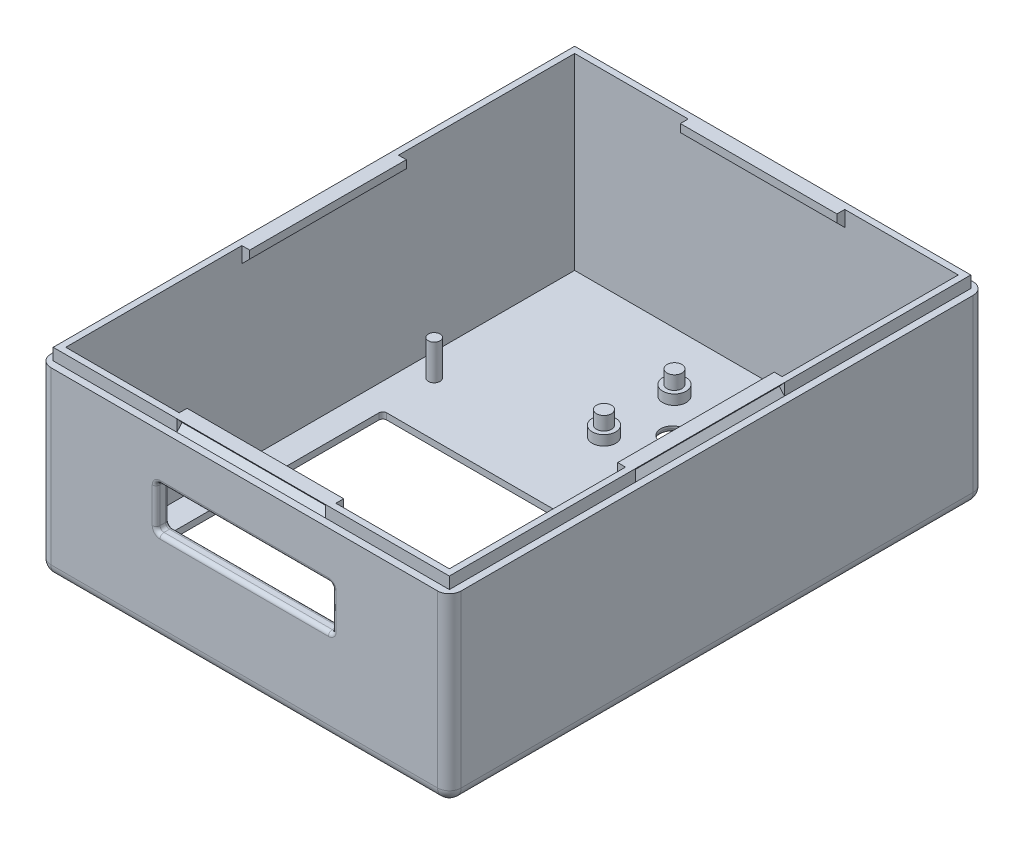
SolidWorks part; units mm, degrees
ref_plane "Plan de face" through (0, 0, 0) normal (0, 0, 1) x (1, 0, 0)
ref_plane "Plan de dessus" through (0, 0, 0) normal (0, 1, 0) x (1, 0, 0)
ref_plane "Plan de droite" through (0, 0, 0) normal (1, 0, 0) x (0, 0, -1)
sketch "Esquisse6" plane through (0, 0, 0) normal (0, 1, 0) x (1, 0, 0)
  line L1 (-49, -65) -> (49, -65)
  line L2 (-49, -65) -> (-49, 65)
  line L3 (-49, 65) -> (49, 65)
  line L4 (49, -65) -> (49, 65)
  line L5 (-49, -65) -> (49, 65) construction
  line L6 (-49, 65) -> (49, -65) construction
  point P1 (0, 0)
  dimension "D1" = 98
  dimension "D2" = 130
extrude "Boss.-Extru.4" add sketch "Esquisse6" along normal blind 48 contours L2 L3 L4 L1
shell "Coque7" thickness 1.6 removed face at (0, 48, 0) outward yes
sketch "Esquisse7" plane through (0, 0, 0) normal (0, 1, 0) x (1, 0, 0)
  line L1 (-49, -65) -> (49, -65)
  line L2 (-49, -65) -> (-49, 65)
  line L3 (-49, 65) -> (49, 65)
  line L4 (49, -65) -> (49, 65)
  line L5 (-49, -65) -> (49, 65) construction
  line L6 (-49, 65) -> (49, -65) construction
  point P0 (0, 0)
  dimension "D1" = 98
  dimension "D2" = 130
extrude "Extru.-Mince1" add sketch "Esquisse7" along normal blind 45 and the other way blind 1.6 separate body thin thin type one direction wall 3.4
sketch "Esquisse13" plane through (0, -1.6, 0) normal (0, -1, 0) x (-1, 0, 0)
  line L0 (0, -22.25) -> (-49, -22.25) construction
  line L1 (-49, 65) -> (49, 65)
  line L2 (-49, 65) -> (-49, -65)
  line L3 (-49, -65) -> (49, -65)
  line L4 (49, 65) -> (49, -65)
  line L5 (-49, 65) -> (49, -65) construction
  line L6 (-49, -65) -> (49, 65) construction
  line L7 (42.5, -54) -> (-42.5, -54)
  line L8 (42.5, -54) -> (42.5, 9.5)
  line L9 (42.5, 9.5) -> (-42.5, 9.5)
  line L10 (-42.5, -54) -> (-42.5, 9.5)
  line L11 (42.5, -54) -> (-42.5, 9.5) construction
  line L12 (42.5, 9.5) -> (-42.5, -54) construction
  line L13 (0, -22.25) -> (49, -22.25) construction
  line L15 (46.1493, 17.8641) -> (-46.1493, 17.8641) construction
  line L16 (46.1493, 17.8641) -> (46.1493, -62.3641) construction
  line L17 (46.1493, -62.3641) -> (-46.1493, -62.3641) construction
  line L18 (-46.1493, 17.8641) -> (-46.1493, -62.3641) construction
  line L19 (46.1493, 17.8641) -> (-46.1493, -62.3641) construction
  line L20 (46.1493, -62.3641) -> (-46.1493, 17.8641) construction
  point P4 (0, 0)
  point P11 (0, -22.25)
  dimension "D1" = 85
  dimension "D2" = 63.5
  dimension "D3" = 11
extrude "Enlèv. mat.-Extru.10" cut sketch "Esquisse13" against normal blind 8 contours L8 L9 L10 L7
sketch "Esquisse16" plane through (0, 0, 0) normal (0, 1, 0) x (1, 0, 0)
  line L0 (0, -18.875) -> (49, -18.875) construction
  line L1 (49, -65) -> (-49, -65) construction
  line L2 (49, -65) -> (49, 65) construction
  line L3 (49, 65) -> (-49, 65) construction
  line L4 (-49, -65) -> (-49, 65) construction
  line L5 (49, -65) -> (-49, 65) construction
  line L6 (49, 65) -> (-49, -65) construction
  line L7 (43.125, -61) -> (-43.125, -61) construction
  line L8 (43.125, -61) -> (43.125, 23.25) construction
  line L9 (43.125, 23.25) -> (-43.125, 23.25) construction
  line L10 (-43.125, -61) -> (-43.125, 23.25) construction
  line L11 (43.125, -61) -> (-43.125, 23.25) construction
  line L12 (43.125, 23.25) -> (-43.125, -61) construction
  line L13 (0, -18.875) -> (-49, -18.875) construction
  circle A0 centre (43.125, 23.25) radius 1.5
  circle A1 centre (43.125, -61) radius 1.5
  circle A2 centre (-43.125, -61) radius 1.5
  circle A3 centre (-43.125, 23.25) radius 1.5
  point P4 (0, 0)
  point P11 (0, -18.875)
  dimension "D1" = 86.25
  dimension "D2" = 84.25
  dimension "D4" = 4
extrude "Boss.-Extru.9" add sketch "Esquisse16" along normal blind 9
sketch "Esquisse17" plane through (0, 0, 0) normal (0, 1, 0) x (1, 0, 0)
  line L1 (16.5, 32) -> (-8.5, 32) construction
  line L2 (16.5, 32) -> (16.5, 50) construction
  line L3 (16.5, 50) -> (-8.5, 50) construction
  line L4 (-8.5, 32) -> (-8.5, 50) construction
  line L5 (16.5, 32) -> (-8.5, 50) construction
  line L6 (16.5, 50) -> (-8.5, 32) construction
  line L7 (0, 0) -> (0, 87.762) construction
  line L11 (-49, 65) -> (49, 65) construction
  circle A0 centre (16.5, 32) radius 3
  circle A1 centre (16.5, 50) radius 3
  circle A2 centre (-8.5, 50) radius 3
  circle A3 centre (-8.5, 32) radius 3
  circle A4 centre (0, 41) radius 3
  circle A5 centre (16.5, 32) radius 1.9
  circle A6 centre (16.5, 50) radius 1.9
  circle A7 centre (-8.5, 32) radius 1.9
  circle A8 centre (-8.5, 50) radius 1.9
  point P4 (4, 41)
  dimension "D4" = 8.5
  dimension "D5" = 15
  dimension "D1" = 18
  dimension "D2" = 25
extrude "Boss.-Extru.10" add sketch "Esquisse17" along normal blind 2.54 contours A1 | A0 | A3 | A2
extrude "Enlèv. mat.-Extru.11" cut sketch "Esquisse17<4>" against normal blind 6 contours A4
sketch "Esquisse17<4>" plane through (0, 0, 0) normal (0, 1, 0) x (1, 0, 0) same geometry as "Esquisse17"
fillet "Congé5" radius 3 8 edges at (0, -1.6, 68.4) (52.4, 21.7, -68.4) (52.4, -1.6, 0) (0, -1.6, -68.4) (-52.4, -1.6, 0) (-52.4, 21.7, -68.4) (-52.4, 21.7, 68.4) (52.4, 21.7, 68.4)
fillet "Congé6" radius 1 4 edges at (-42.5, -0.8, 54) (42.5, -0.8, 54) (42.5, -0.8, -9.5) (-42.5, -0.8, -9.5)
sketch "Esquisse22" plane through (0, 0, 68.4) normal (0, 0, 1) x (1, 0, 0)
  line L0 (-49.4, 45) -> (-49.4, 1.4) construction
  line L1 (-22.5, 33) -> (22.5, 33)
  line L2 (-22.5, 33) -> (-22.5, 22)
  line L3 (-22.5, 22) -> (22.5, 22)
  line L4 (22.5, 33) -> (22.5, 22)
  line L5 (-22.5, 33) -> (22.5, 22) construction
  line L6 (-22.5, 22) -> (22.5, 33) construction
  line L8 (49.4, 1.4) -> (49.4, 45)
  line L9 (49.4, 1.4) -> (49.4, 45) construction
  line L10 (-49.4, 45) -> (49.4, 45) construction
  line L12 (0, 45) -> (0, 1.4) construction
  line L13 (-49.4, 1.4) -> (49.4, 1.4) construction
  line L14 (-50.6, 48) -> (50.6, 48) construction
  line L15 (49.4, 23.2) -> (-49.4, 23.2) construction
  point P0 (0, 27.5)
  dimension "D1" = 26
  dimension "D2" = 45
  dimension "D3" = 11
extrude "Enlèv. mat.-Extru.12" cut sketch "Esquisse22" against normal blind 6 contours L3 L4 L1 L2
fillet "Congé7" radius 1 12 edges at (-22.5, 27.5, 65) (22.5, 27.5, 65) (22.5, 27.5, 68.4) (-22.5, 27.5, 68.4) (-22.5, 33, 66.7) (0, 33, 68.4) (22.5, 33, 66.7) (0, 33, 65) (0, 22, 65) (22.5, 22, 66.7) (0, 22, 68.4) (-22.5, 22, 66.7)
sketch3d "Esquisse3D2"
  line L0 (49, 46, 0) -> (49, 44, 0)
  line L5 (49, 48, 65) -> (49, 48, -65) construction
  line L6 (49, 48, 0) -> (47, 48, 0)
  line L11 (49, 48, 0) -> (49, 46, 0)
  line L13 (47, 48, 0) -> (47, 46, 0)
  line L14 (49, 48, 0) -> (47, 46, 0) construction
  line L15 (49, 46, 0) -> (47, 48, 0) construction
  line L16 (49, 44, 0) -> (47, 46, 0)
  point P8 (48, 47, 0)
  dimension "D1" = 2
extrude "Boss.-Extru.15" add sketch "Esquisse3D2" along direction (0, 0, -1) on the side of the normal blind 20 and the other way blind 20
mirror "Symétrie1" about plane through (0, 0, 0) normal (1, 0, 0) of "Boss.-Extru.15"
sketch3d "Esquisse3D4"
  line L0 (-49, 48, -65) -> (49, 48, -65) construction
  line L1 (0, 48, -65) -> (0, 48, -63)
  line L2 (0, 48, -65) -> (0, 46, -65)
  line L4 (0, 48, -63) -> (0, 46, -63)
  line L5 (0, 48, -65) -> (0, 46, -63) construction
  line L6 (0, 46, -65) -> (0, 48, -63) construction
  line L7 (0, 46, -65) -> (0, 44, -65)
  line L8 (0, 44, -65) -> (0, 46, -63)
  point P5 (0, 47, -64)
  dimension "D1" = 2
extrude "Boss.-Extru.16" add sketch "Esquisse3D4" along direction (-1, 0, 0) on the side of the normal blind 20 and the other way blind 20
sketch3d "Esquisse3D6"
  line L0 (50.6, 48, 0) -> (50.6, 45, 0)
  line L1 (50.6, 48, 66.6) -> (50.6, 48, -66.6) construction
  line L2 (50.6, 45, -66.6) -> (50.6, 45, 66.6) construction
  line L3 (50.6, 45, 0) -> (49.2771, 46.5, 0)
  line L4 (49.2771, 46.5, 0) -> (50.6, 48, 0)
  dimension "D1" = 2
extrude "Enlèv. mat.-Extru.14" cut sketch "Esquisse3D6" along direction (0, 0, -1) on the side against the normal blind 19 and the other way blind 19
mirror "Symétrie2" about plane through (0, 0, 0) normal (1, 0, 0) of "Enlèv. mat.-Extru.14"
mirror "Symétrie3" about plane through (0, 0, 0) normal (0, 0, 1) of "Boss.-Extru.16"
sketch3d "Esquisse3D7"
  line L0 (0, 48, -66.6) -> (0, 45, -66.6)
  line L1 (-50.6, 48, -66.6) -> (50.6, 48, -66.6) construction
  line L2 (50.6, 45, -66.6) -> (-50.6, 45, -66.6) construction
  line L3 (0, 45, -66.6) -> (0, 46.5, -65.2771)
  line L4 (0, 46.5, -65.2771) -> (0, 48, -66.6)
  dimension "D1" = 2
extrude "Enlèv. mat.-Extru.15" cut sketch "Esquisse3D7" along direction (-1, 0, 0) on the side against the normal blind 19 and the other way blind 19
mirror "Symétrie5" about plane through (0, 0, 0) normal (0, 0, 1) of "Enlèv. mat.-Extru.15"
fillet "Congé8" radius 1 1 edges at (0, -1.6, -38)
extrude "Boss.-Extru.18" add sketch "Esquisse17<7>" along normal blind 6 contours A5 | A7 | A8 | A6
sketch "Esquisse17<7>" plane through (0, 0, 0) normal (0, 1, 0) x (1, 0, 0) same geometry as "Esquisse17"
